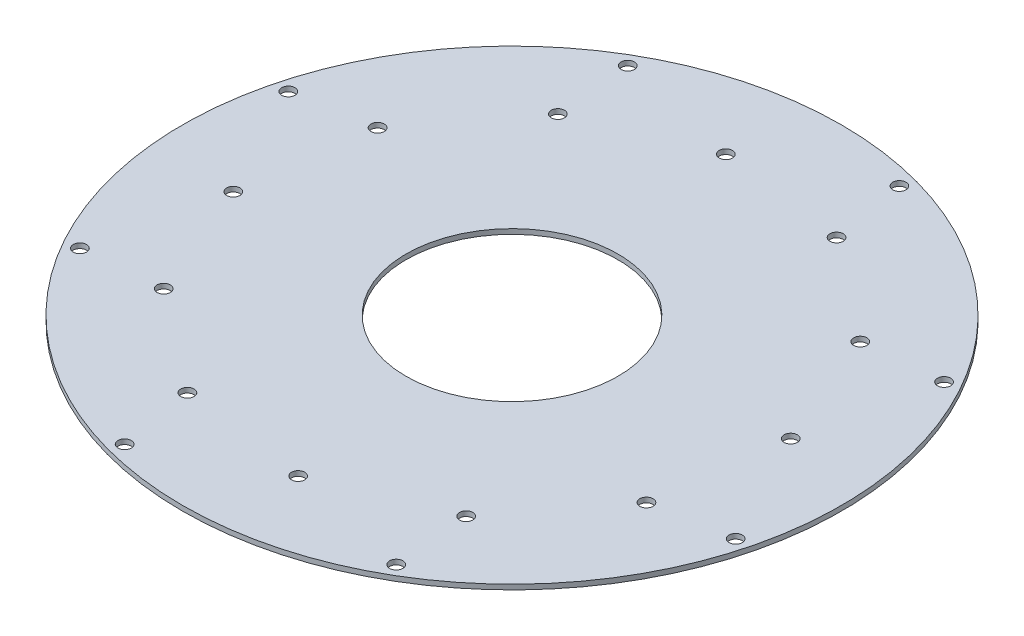
SolidWorks part; units mm, degrees
material "Thornel Mat VMA"
ref_plane "Front Plane" through (0, 0, 0) normal (0, 0, 1) x (1, 0, 0)
ref_plane "Top Plane" through (0, 0, 0) normal (0, 1, 0) x (1, 0, 0)
ref_plane "Right Plane" through (0, 0, 0) normal (1, 0, 0) x (0, 0, -1)
sketch "Sketch1" plane through (0, 0, 0) normal (0, 1, 0) x (1, 0, 0)
  circle A0 centre (0, 0) radius 32
  circle A1 centre (0, 0) radius 99.5
  dimension "D1" = 64
  dimension "D2" = 199
extrude "Base" add sketch "Sketch1" along normal mid plane 1.5
sketch "Sketch2" plane through (0, 0.75, 0) normal (0, 1, 0) x (1, 0, 0)
  line L0 (24.7172, 92.2459) -> (25.7525, 96.1096) construction
  line L1 (24.7172, 92.2459) -> (0, 0) construction
  line L2 (0, 0) -> (0, 99.5) construction
  circle A0 centre (24.7172, 92.2459) radius 2
  circle A2 centre (0, 0) radius 99.5 construction
  dimension "D1" = 4
  dimension "D2" = 4
  dimension "D3" = 15
extrude "Structural Hole" cut sketch "Sketch2" against normal through all
pattern_circular "Structural Hole Pattern" count 8 over 360 about axis through (0, 0.75, 0) along (0, -1, 0) of "Structural Hole" reverse direction yes
sketch "Sketch3" plane through (0, 0.75, 0) normal (0, 1, 0) x (1, 0, 0)
  line L0 (0, 0) -> (-9.7895, 74.3584) construction
  line L1 (0, 0) -> (0, 99.5) construction
  line L2 (-47.75, 82.7054) -> (0, 0) construction
  line L3 (0, 0) -> (24.7172, 92.2459) construction
  circle A0 centre (0, 0) radius 99.5 construction
  circle A1 centre (-9.7895, 74.3584) radius 2
  dimension "D3" = 4
  dimension "D1" = 7.5
  dimension "D2" = 75
extrude "Cut-Extrude1" cut sketch "Sketch3" against normal through all
pattern_circular "CirPattern1" count 12 over 360 about axis through (0, 0.75, 0) along (0, 1, 0) of "Cut-Extrude1"
equation "\"lift_fan_diameter\"=64"
equation "\"D1@Sketch1\"=\"lift_fan_diameter\""
equation "\"outer_diameter\"=199"
equation "\"D2@Sketch1\"=\"outer_diameter\""
equation "\"bolt_diameter\"=4"
equation "\"D1@Sketch2\"=\"bolt_diameter\""
equation "\"wall_thickness\"= 4"
equation "\"D2@Sketch2\"=\"wall_thickness\""
